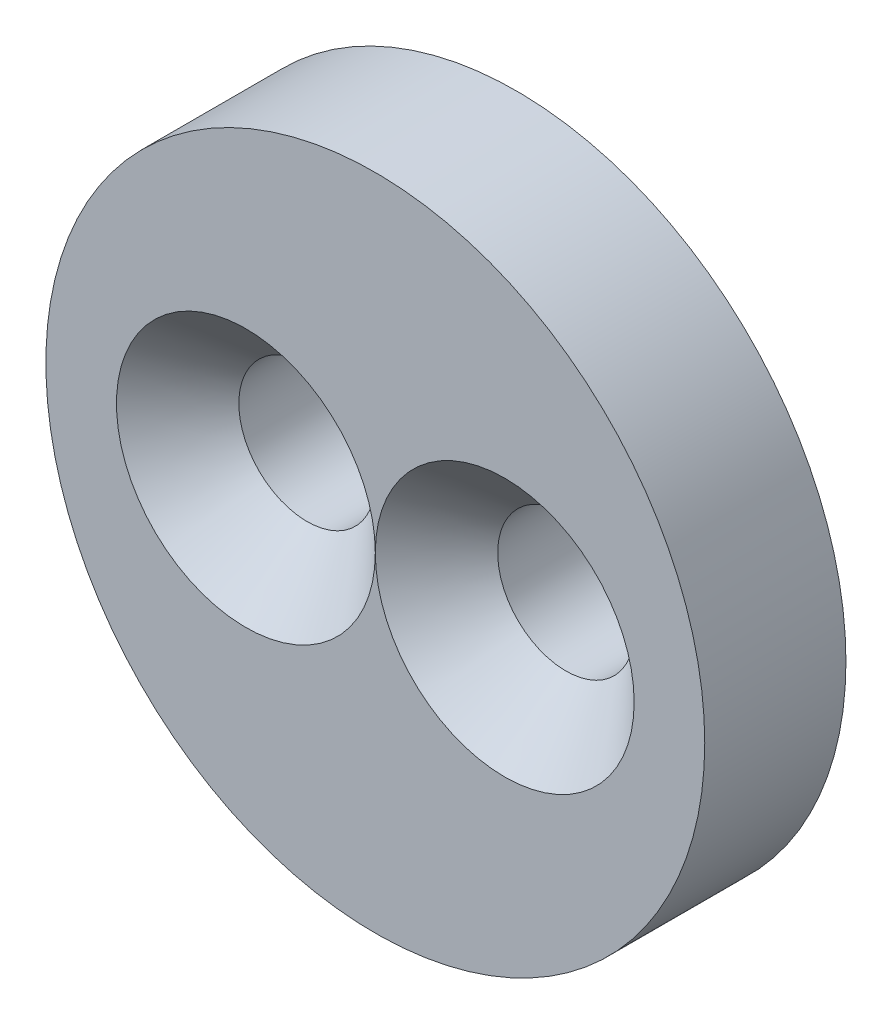
SolidWorks part; units mm, degrees
ref_plane "Front Plane" through (0, 0, 0) normal (0, 0, 1) x (1, 0, 0)
ref_plane "Top Plane" through (0, 0, 0) normal (0, 1, 0) x (1, 0, 0)
ref_plane "Right Plane" through (0, 0, 0) normal (1, 0, 0) x (0, 0, -1)
sketch "Sketch1" plane through (0, 0, 26.85) normal (0, 0, 1) x (1, 0, 0)
  circle A0 centre (0, 0) radius 7
  circle A1 centre (0, 0) radius 7.4923 construction
  dimension "D1" = 14
extrude "Boss-Extrude1" add sketch "Sketch1" along normal blind 3
hole_wizard "CSK for M2.5 Countersunk Flat Head Screw1" positions "Sketch2" profile "Sketch4" countersink size "M2.5" standard "ISO" end condition through all
sketch "Sketch2" plane through (0, 0, 29.85) normal (0, 0, 1) x (1, 0, 0)
  point P0 (-2.75, 0)
  point P3 (2.75, 0)
sketch "Sketch4" plane through (-2.75, 0, 29.85) normal (1, 0, 0) x (0, -1, 0)
  line L0 (0, 0) -> (0, 3)
  line L1 (0, 3) -> (1.45, 3)
  line L2 (1.45, 3) -> (1.45, 1.3)
  line L3 (1.45, 1.3) -> (2.75, 0)
  line L5 (2.75, 0) -> (0, 0)
  line L6 (-1.45, 1.3) -> (-2.75, 0) construction
  line L11 (0, -6.35) -> (0, 107.95) construction
  dimension "Thru Hole Dia." = 2.9
  dimension "Thru Hole Depth" = 3
  dimension "Near C'Sink Dia." = 5.5
  dimension "Near C'Sink Angle" = 90
